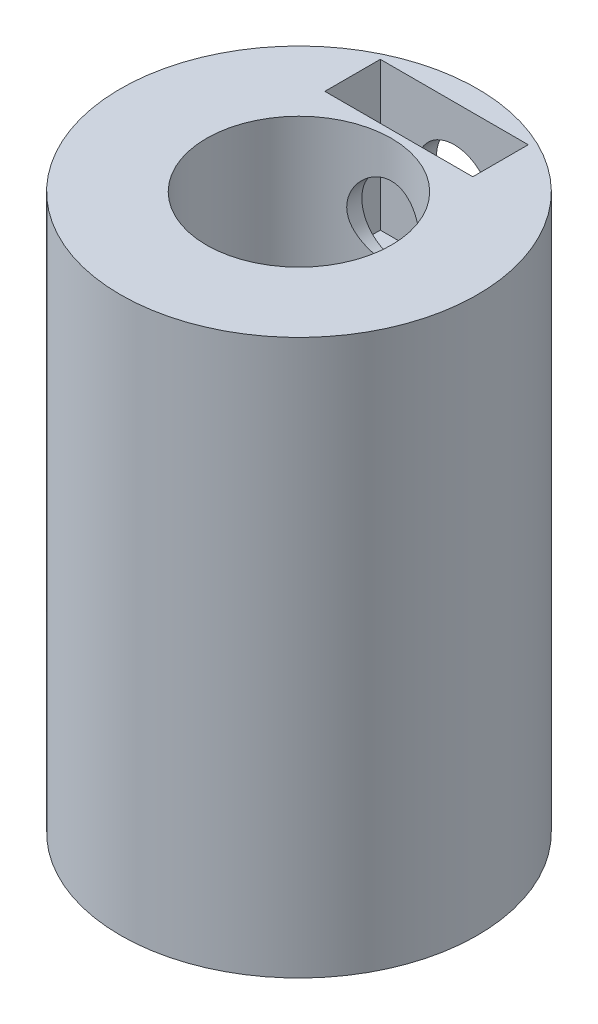
SolidWorks part; units mm, degrees
note: The reader was unsure of these and kept them because the rebuilt part matched: shared geometry of "Çizim1<6>".
ref_plane "Ön Düzlem" through (0, 0, 0) normal (0, 0, 1) x (1, 0, 0)
ref_plane "Üst Düzlem" through (0, 0, 0) normal (0, 1, 0) x (1, 0, 0)
ref_plane "Sağ Düzlem" through (0, 0, 0) normal (1, 0, 0) x (0, 0, -1)
sketch "Çizim1" plane through (0, 0, 0) normal (0, 1, 0) x (1, 0, 0)
  circle A2 centre (0, 0) radius 4.825
  circle A3 centre (0, 0) radius 2.5
  dimension "D1" = 5
  dimension "D3" = 9.65
extrude "Boss-Extrude1" add sketch "Çizim1" along normal blind 15
extrude "Cut-Extrude1" cut sketch "Çizim1<6>" along normal blind 3
sketch "Çizim1<6>" plane through (0, 0, 0) normal (0, 1, 0) x (1, 0, 0) same geometry as "Çizim1"
sketch "Sketch2" plane through (0, 15, 0) normal (0, 1, 0) x (1, 0, 0)
  circle A0 centre (0, 0) radius 2.5
  dimension "D1" = 5
extrude "Cut-Extrude2" cut sketch "Sketch2" against normal blind 5
sketch "Sketch3" plane through (0, 0, 0) normal (0, 0, 1) x (1, 0, 0)
  line L0 (4.825, 15) -> (-4.825, 15) construction
  circle A0 centre (0, 13) radius 1
  dimension "D1" = 2
  dimension "D2" = 2
extrude "Cut-Extrude3" cut sketch "Sketch3" against normal through all
sketch "Çizim2" plane through (0, 15, 0) normal (0, 1, 0) x (1, 0, 0)
  line L1 (-2, 4.2) -> (2, 4.2)
  line L2 (-2, 4.2) -> (-2, 2.7)
  line L3 (-2, 2.7) -> (2, 2.7)
  line L4 (2, 4.2) -> (2, 2.7)
  point P4 (0, 4.2)
  dimension "D1" = 4
  dimension "D2" = 1.5
  dimension "D3" = 2.7
extrude "Kes-Ekstrüzyon1" cut sketch "Çizim2" against normal blind 4
